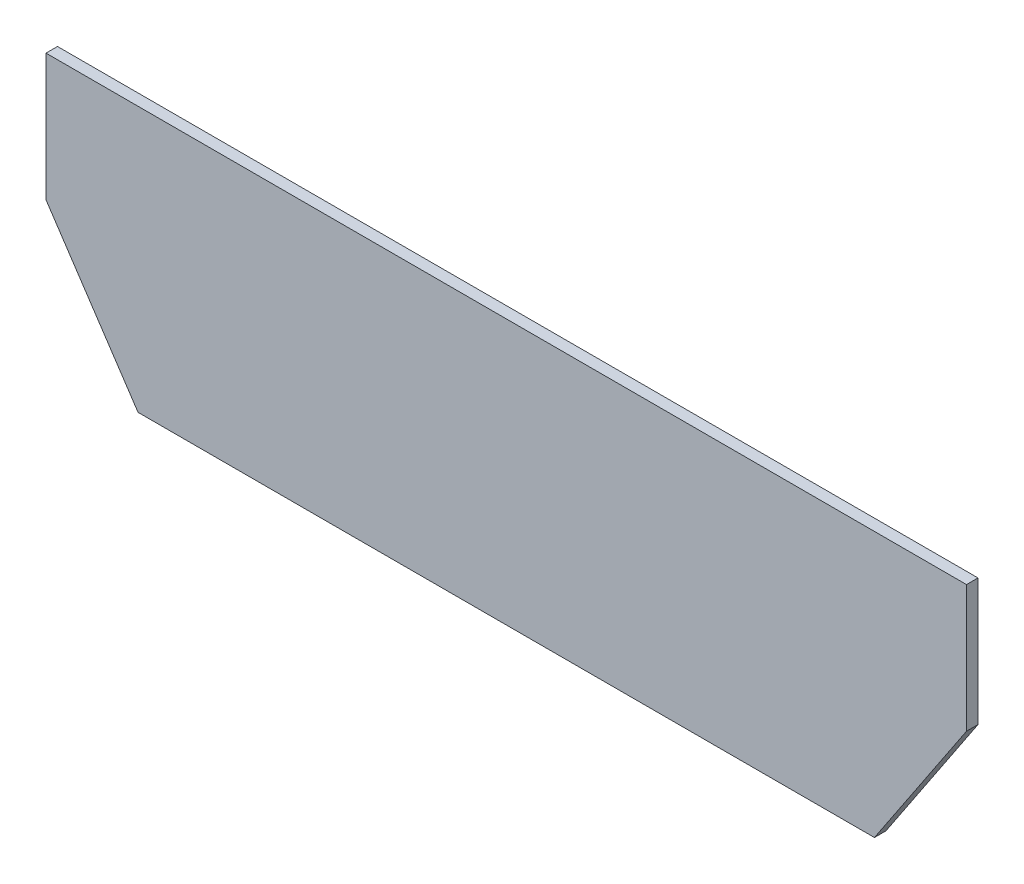
SolidWorks part; units mm, degrees
ref_plane "Front Plane" through (0, 0, 0) normal (0, 0, 1) x (1, 0, 0)
ref_plane "Top Plane" through (0, 0, 0) normal (0, 1, 0) x (1, 0, 0)
ref_plane "Right Plane" through (0, 0, 0) normal (1, 0, 0) x (0, 0, -1)
sketch "Sketch1" plane through (0, 0, 0) normal (0, 0, 1) x (1, 0, 0)
  line L12 (22.225, 2.286) -> (123.825, 2.286)
  line L13 (123.825, 2.286) -> (136.525, 21.336)
  line L14 (136.525, 21.336) -> (136.525, 38.862)
  line L15 (136.525, 38.862) -> (9.525, 38.862)
  line L16 (9.525, 38.862) -> (9.525, 21.336)
  line L17 (9.525, 21.336) -> (22.225, 2.286)
extrude "Boss-Extrude1" add sketch "Sketch1" along normal blind 1.5875
